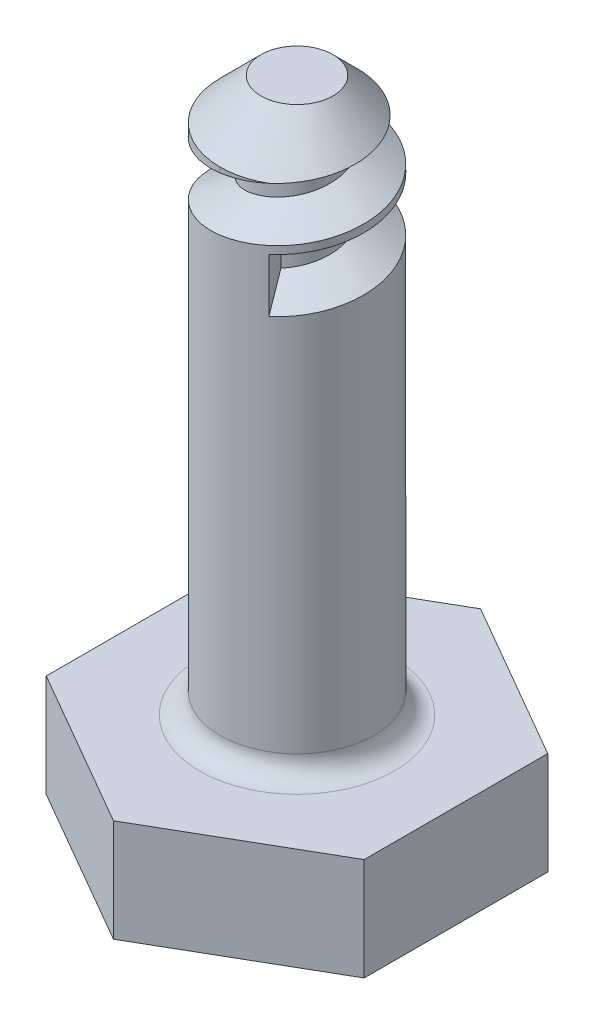
SolidWorks part; units mm, degrees
ref_plane "Front Plane" through (0, 0, 0) normal (0, 0, 1) x (1, 0, 0)
ref_plane "Top Plane" through (0, 0, 0) normal (0, 1, 0) x (1, 0, 0)
ref_plane "Right Plane" through (0, 0, 0) normal (1, 0, 0) x (0, 0, -1)
sketch "Sketch3" plane through (0, 0, 0) normal (0, 1, 0) x (1, 0, 0)
  line L1 (7.75, -4.4745) -> (7.75, 4.4745)
  line L2 (7.75, 4.4745) -> (0, 8.9489)
  line L3 (0, 8.9489) -> (-7.75, 4.4745)
  line L4 (-7.75, 4.4745) -> (-7.75, -4.4745)
  line L5 (-7.75, -4.4745) -> (0, -8.9489)
  line L6 (0, -8.9489) -> (7.75, -4.4745)
  circle A0 centre (0, 0) radius 7.75 construction
  circle A1 centre (0, 0) radius 3.75
  dimension "D2" = 7.5
  dimension "D1" = 4
extrude "Boss-Extrude1" add sketch "Sketch3" against normal blind 5 contours L5 L6 L1 L2 L3 L4 A1 | A1 region at (3.7566, 0, 6.5067) region at (0, 0, 0)
extrude "Boss-Extrude2" add sketch "Sketch3<3>" along normal blind 27 and the other way blind 3 contours A1 region at (0, 0, 0)
sketch "Sketch3<3>" plane through (0, 0, 0) normal (0, 1, 0) x (1, 0, 0) same geometry as "Sketch3"
chamfer "Chamfer1" distance 2 angle 45 1 edges at (0, 27, 3.75)
thread "Thread1" pitch 3 method cut trim with start face yes profile "Thread Profile1" start angle 0, offset 0, length 5, pitch 3, diameter 7.5
ref_plane "Plane1" through (-3.75, 27, 0) normal (0, 0, 1) x (-1, 0, 0)
sketch "Thread Profile1" plane through (-3.75, 27, 0) normal (0, 0, 1) x (-1, 0, 0)
  line L0 (0, 0) -> (0, 3) construction
  line L11 (0, 0) -> (0, 2.625)
  line L12 (0, 2.625) -> (-1.6238, 1.6875)
  line L13 (-1.6238, 1.6875) -> (-1.6238, 0.9375)
  line L15 (-1.6238, 0.9375) -> (0, 0)
  line L17 (-1.6238, 1.3125) -> (0, 1.3125) construction
  point P2 (0, 0)
  dimension "Pitch" = 3
  dimension "Profile_Angle" = 60
  dimension "Profile_Land" = 0.75
  dimension "Profile_Height" = 1.6238
fillet "Fillet2" radius 1 1 edges at (0, 0, 3.75)
equation "\"diameter\"= 7.5"
equation "\"shoulderLength\" = 22"
equation "\"screwLength\" = 5"
equation "\"D2@Sketch3\"=\"diameter\""
equation "\"D4@Thread1\"=\"screwLength\""
equation "\"D1@Boss-Extrude2\"=\"shoulderLength\"+\"screwLength\""
